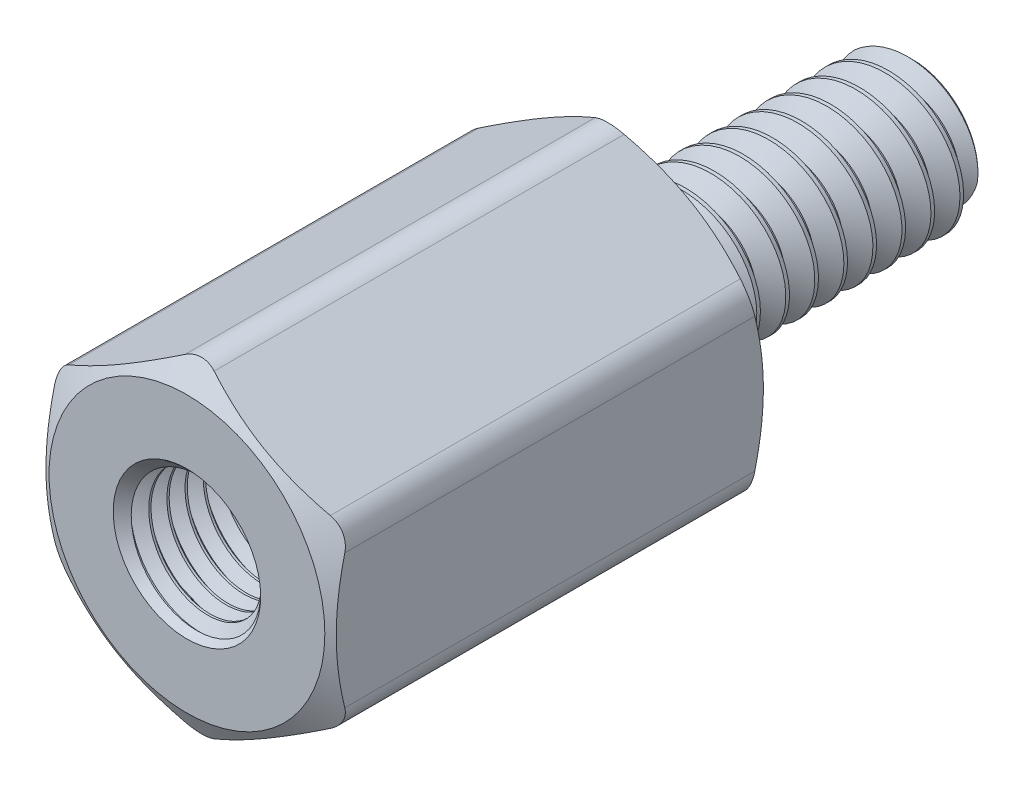
SolidWorks part; units mm, degrees
ref_plane "Front Plane" through (0, 0, 0) normal (0, 0, 1) x (1, 0, 0)
ref_plane "Top Plane" through (0, 0, 0) normal (0, 1, 0) x (1, 0, 0)
ref_plane "Right Plane" through (0, 0, 0) normal (1, 0, 0) x (0, 0, -1)
sketch "Sketch1" plane through (0, 0, 0) normal (0, 0, 1) x (1, 0, 0)
  line L1 (6.35, 3.6662) -> (0, 7.3323)
  line L2 (0, 7.3323) -> (-6.35, 3.6662)
  line L3 (-6.35, 3.6662) -> (-6.35, -3.6662)
  line L4 (-6.35, -3.6662) -> (0, -7.3323)
  line L5 (0, -7.3323) -> (6.35, -3.6662)
  line L6 (6.35, -3.6662) -> (6.35, 3.6662)
  circle A0 centre (0, 0) radius 6.35 construction
  point P10 (0, -6.35)
  dimension "Hex Size" = 12.7
sketch "Sketch2" plane through (0, 0, 0) normal (1, 0, 0) x (0, 0, -1)
  line L0 (12.7, 0) -> (-19.05, 0) construction
  line L2 (0, 3.175) -> (0, -3.175) construction
  line L3 (-5.9436, 3.175) -> (-5.9436, -3.175) construction
  line L4 (-19.7941, 3.2609) -> (-19.3973, 2.5735) construction
  line L5 (-19.3973, 2.5735) -> (-19.0004, 3.2609) construction
  line L6 (-19.0004, 3.2609) -> (-19.7941, 3.2609) construction
  line L7 (-19.7445, 3.175) -> (-19.05, 3.175) construction
  line L8 (-19.4469, 2.6594) -> (-19.3477, 2.6594) construction
  line L9 (-19.3973, 2.6594) -> (-19.3973, 2.5735) construction
  line L10 (-19.3973, 3.175) -> (-19.3973, 3.2609) construction
  line L11 (12.6206, 3.3125) -> (13.8906, 3.3125) construction
  line L12 (13.8906, 3.3125) -> (13.2556, 2.2126) construction
  line L13 (13.2556, 2.2126) -> (12.6206, 3.3125) construction
  line L14 (12.7, 3.175) -> (13.8113, 3.175) construction
  line L15 (13.1763, 2.3501) -> (13.335, 2.3501) construction
  line L16 (13.2556, 2.3501) -> (13.2556, 2.2126) construction
  line L17 (13.2556, 3.175) -> (13.2556, 3.3125) construction
  line L18 (0, 7.3323) -> (-19.05, 7.3323) construction
  point P6 (0, 0)
  point P9 (-5.9436, 0)
  dimension "Length" = 19.05
sketch "Sketch3" plane through (0, 0, 0) normal (1, 0, 0) x (0, 0, -1)
  line L0 (-5.9436, 0) -> (12.7, 0)
  line L1 (-5.9436, 3.175) -> (-5.9436, -3.175) construction
  line L2 (12.7, 0) -> (12.7, 2.8575)
  line L3 (12.7, 2.8575) -> (12.3825, 3.175)
  line L4 (12.3825, 3.175) -> (2.0002, 3.175)
  line L5 (2.0002, 3.175) -> (1.524, 2.3501)
  line L6 (-5.9436, 0) -> (-5.9436, 2.8575)
  line L7 (-5.9436, 2.8575) -> (-6.2611, 3.175)
  line L8 (-6.2611, 3.175) -> (-18.7325, 3.175)
  line L9 (-18.7325, 3.175) -> (-19.05, 3.4925)
  line L10 (12.3825, 0) -> (12.3825, -3.175) construction
  line L11 (-19.05, 3.4925) -> (-19.05, 6.35)
  line L12 (-19.05, 6.35) -> (0, 6.35)
  line L14 (1.524, 2.3501) -> (0.3175, 2.3501)
  line L15 (0, 2.6676) -> (0, 6.35)
  arc A0 (0, 2.6676) -> (0.3175, 2.3501) centre (0.3175, 2.6676) ccw
  point P5 (-19.05, -6.35)
  point P8 (-17.0656, -3.175)
  point P9 (9.525, -3.175)
  point P27 (0, 2.3501)
  dimension "D4" = 0.3175
  dimension "D2" = 0.3175
  dimension "D1" = 45
  dimension "D6" = 3.175
  dimension "D7" = 60
  dimension "D3" = 1.9844
  dimension "D5" = 1.524
revolve "Revolve1" add sketch "Sketch3" angle 360 about L0
sketch "Sketch4" plane through (0, 0, 19.05) normal (0, 0, 1) x (1, 0, 0)
  line L0 (0, 6.35) -> (0, 3.175) construction
  line L1 (-6.35, 3.6662) -> (-6.35, -3.6662)
  line L2 (-6.35, -3.6662) -> (0, -7.3323)
  line L3 (0, -7.3323) -> (6.35, -3.6662)
  line L4 (6.35, -3.6662) -> (6.35, 3.6662)
  line L5 (6.35, 3.6662) -> (0, 7.3323)
  line L6 (0, 7.3323) -> (-6.35, 3.6662)
  circle A0 centre (0, 0) radius 6.35 construction
  circle A1 centre (0, 0) radius 4.7625
  circle A2 centre (0, 0) radius 6.35 construction
  point P16 (0, 4.7625)
extrude "Boss-Extrude1" add sketch "Sketch4" against normal up to surface (19.05 mm away) up to face at (0, 6.35, 0)
sketch "Sketch5" plane through (0, 0, 19.05) normal (0, 0, 1) x (1, 0, 0)
  line L0 (-1.8211, 2.6008) -> (1.8211, -2.6008) construction
  line L1 (0, 3.175) -> (0, -3.175) construction
  line L3 (0, -7.8495) -> (0, 7.8495) construction
  circle A0 centre (0, 0) radius 6.0325
  point P11 (1.8211, -2.6008)
  dimension "D1" = 12.065
  dimension "D2" = 35
extrude "Cut-Extrude1" cut sketch "Sketch5" against normal through all draft 60 flip side to cut
sketch "Sketch6" plane through (0, 0, 0) normal (0, 0, -1) x (-1, 0, 0)
  circle A0 centre (0, 0) radius 6.0325
  circle A1 centre (0, 0) radius 6.0325 construction
extrude "Cut-Extrude2" cut sketch "Sketch6" against normal through all draft 60 flip side to cut
fillet "Fillet1" radius 1.27 6 edges at (0, 7.3323, 9.525) (-6.35, -3.6662, 9.525) (0, -7.3323, 9.525) (6.35, -3.6662, 9.525) (6.35, 3.6662, 9.525) (-6.35, 3.6662, 9.525)
sketch "Drawing1" plane through (0, 0, 0) normal (1, 0, 0) x (0, 0, -1)
  line L0 (-19.05, 3.175) -> (-5.9436, 3.175) construction
  line L1 (-5.9436, 3.175) -> (-5.9436, -3.175) construction
  line L2 (-5.9436, -3.175) -> (-19.05, -3.175) construction
sketch "Sketch7" plane through (0, 0, 0) normal (-1, 0, 0) x (0, 0, 1)
  line L0 (-13.1763, 2.3501) -> (-13.335, 2.3501)
  line L1 (-13.335, 2.3501) -> (-13.8509, 3.2437)
  line L2 (-13.8906, 3.3125) -> (-13.2556, 2.2126) construction
  line L3 (-13.8509, 3.2437) -> (-12.6603, 3.2437)
  line L4 (-13.2556, 2.2126) -> (-12.6206, 3.3125) construction
  line L5 (-12.6603, 3.2437) -> (-13.1763, 2.3501)
  line L6 (-13.2556, 3.175) -> (-13.2556, 3.3125) construction
  point P12 (-13.2556, 3.2437)
sketch "Sketch8" plane through (0, 0, -12.7) normal (0, 0, -1) x (-1, 0, 0)
  circle A0 centre (0, 0) radius 3.175
curve "Helix/Spiral1" pitch 1.27 height 12.319 turns 9.7
sweep "Cut-Sweep1" cut profiles "Sketch7" path "Helix/Spiral1"
sketch "Sketch9" plane through (0, 0, 5.9436) normal (0, 0, 1) x (1, 0, 0)
  circle A0 centre (0, 0) radius 3.4925
extrude "Boss-Extrude2" add sketch "Sketch9" along normal up to surface (13.1064 mm away)
sketch "Sketch10" plane through (0, 0, 0) normal (1, 0, 0) x (0, 0, -1)
  line L0 (12.7, 0) -> (-19.05, 0) construction
  line L1 (-5.9436, 3.175) -> (-19.05, 3.175)
  line L2 (-5.9436, 3.175) -> (-5.9436, 0)
  line L3 (-5.9436, 0) -> (-19.05, 0)
  line L4 (-19.05, 3.175) -> (-19.05, 0)
revolve "Revolve2" add sketch "Sketch10" angle 360 about L0
sketch "Sketch11" plane through (0, 0, 19.05) normal (0, 0, 1) x (1, 0, 0)
  circle A0 centre (0, 0) radius 3.175
  circle A1 centre (0, 0) radius 3.175 construction
sketch "Sketch12" plane through (0, 0, 0) normal (1, 0, 0) x (0, 0, -1)
  line L0 (-19.4469, 2.6594) -> (-19.3477, 2.6594)
  line L1 (-19.3477, 2.6594) -> (-19.0252, 3.218)
  line L2 (-19.3973, 2.5735) -> (-19.0004, 3.2609) construction
  line L3 (-19.0252, 3.218) -> (-19.7693, 3.218)
  line L4 (-19.7941, 3.2609) -> (-19.3973, 2.5735) construction
  line L5 (-19.7693, 3.218) -> (-19.4469, 2.6594)
  line L6 (-19.3973, 3.175) -> (-19.3973, 3.2609) construction
  point P12 (-19.3973, 3.218)
curve "Helix/Spiral2" pitch 0.7937 height 13.9002 turns 17.512
sweep "Cut-Sweep2" cut profiles "Sketch12" path "Helix/Spiral2"
combine bodies "Combine1" operation type subtract main body 113 bodies to subtract 114
sketch "Sketch13" plane through (0, 0, 19.05) normal (0, 0, 1) x (1, 0, 0)
  circle A0 centre (0, 0) radius 3.2258
  dimension "D1" = 0.0508
extrude "Cut-Extrude3" cut sketch "Sketch13" against normal through all draft 45
equation "\"Thread Pitch (B)/8@Sketch2\"=\"Thread Pitch (B)@Sketch2\"/8"
equation "\"Thread Pitch (A)/8@Sketch2\"=\"Thread Pitch (A)@Sketch2\"/8"
equation "\"D1@Sketch5\" = \"Hex Size@Sketch1\" * .95"
equation "\"D1@Fillet1\" = \"Hex Size@Sketch1\" * .1"
equation "\"D2@Sketch3\" = \"Thread Pitch (A)@Sketch2\" * .25"
equation "\"D4@Sketch3\" = \"D2@Sketch3\""
equation "\"D6@Sketch3\" = \"Thread Pitch (A)@Sketch2\" * 2.5"
equation "\"D3@Helix/Spiral1\" = \"Thread Length (A)@Sketch2\" - \"D5@Sketch3\" * .25"
equation "\"D4@Helix/Spiral1\" = \"Thread Pitch (A)@Sketch2\""
equation "\"D3@Sketch3\" = \"Thread Pitch (B)@Sketch2\" * 2.5"
equation "\"D5@Sketch3\" = \"Thread Length (A)@Sketch2\" * .12"
equation "\"D3@Helix/Spiral2\" = \"Minimum Thread Length (B)@Sketch2\" + \"Thread Pitch (B)@Sketch2\""
equation "\"D4@Helix/Spiral2\" = \"Thread Pitch (B)@Sketch2\""
